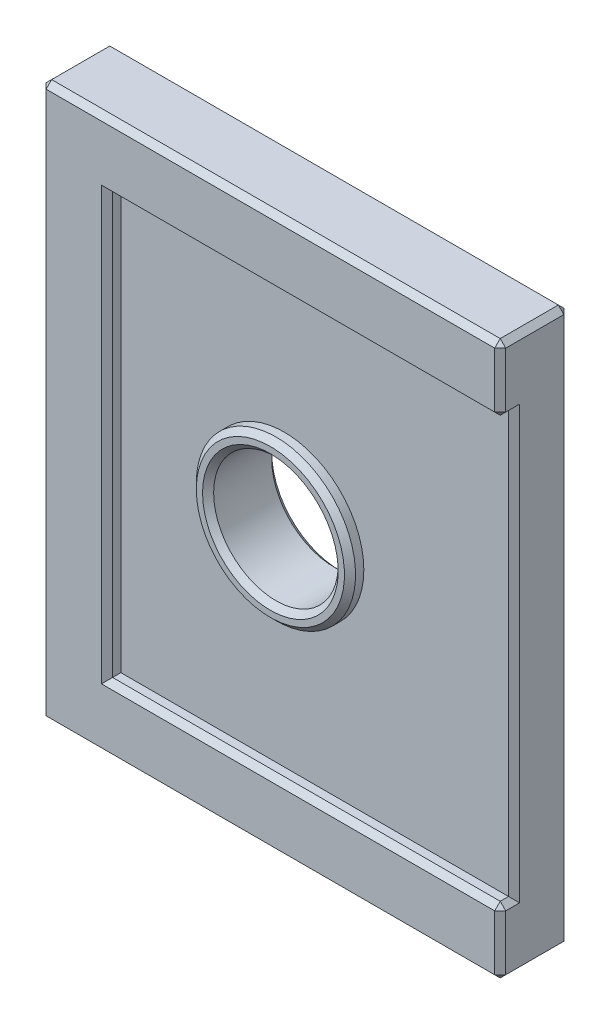
SolidWorks part; units mm, degrees
ref_plane "Front" through (0, 0, 0) normal (0, 0, 1) x (1, 0, 0)
ref_plane "Top" through (0, 0, 0) normal (0, 1, 0) x (1, 0, 0)
ref_plane "Right" through (0, 0, 0) normal (1, 0, 0) x (0, 0, -1)
sketch "Sketch1" plane through (0, 0, 0) normal (0, 0, 1) x (1, 0, 0)
  line L0 (10.1535, 7.5) -> (-5.8, 7.5) construction
  line L1 (-8.3, 10) -> (8.3, 10)
  line L2 (-8.3, 10) -> (-8.3, -10)
  line L3 (-8.3, -10) -> (8.3, -10)
  line L4 (8.3, 10) -> (8.3, -10)
  line L5 (-8.3, 10) -> (8.3, -10) construction
  line L6 (-8.3, -10) -> (8.3, 10) construction
  line L7 (-5.8, 7.5) -> (-5.8, -7.5) construction
  circle A2 centre (0, 0) radius 2.875
  circle A3 centre (0, 0) radius 2.875 construction
  point P0 (0, 0)
  dimension "D1" = 2.5
  dimension "D2" = 2.5
  dimension "D3" = 0.2
extrude "Boss-Extrude1" add sketch "Sketch1" against normal blind 2
sketch "Sketch2" plane through (0, 0, 0) normal (0, 0, 1) x (1, 0, 0)
  line L0 (8.3, 10) -> (-8.3, 10)
  line L1 (-8.3, 10) -> (-8.3, -10)
  line L2 (-8.3, -10) -> (8.3, -10)
extrude "Extrude-Thin1" add sketch "Sketch2" along normal blind 0.5 thin thin type one direction reverse wall 2.4
sketch "Sketch3" plane through (0, 0, 0) normal (0, 0, 1) x (1, 0, 0)
  circle A0 centre (0, 0) radius 2.875 construction
  circle A1 centre (0, 0) radius 2.875
extrude "Boss-Extrude2" add sketch "Sketch3" along normal up to surface (0.5 mm away) up to face at (0.6, 0, 0.5)
sketch "Sketch4" plane through (0, 0, -2) normal (0, 0, -1) x (-1, 0, 0)
  point P0 (0, 0)
hole_wizard "M4 Clearance Hole1" positions "Sketch4" profile "Sketch5" hole size "M4" standard "ANSI Metric" end condition through all
sketch "Sketch5" plane through (0, 0, -2) normal (1, 0, 0) x (0, 1, 0)
  line L0 (0, 0) -> (0, 2.5)
  line L1 (0, 2.5) -> (2.25, 2.5)
  line L2 (2.25, 2.5) -> (2.25, 0)
  line L5 (2.25, 0) -> (0, 0)
  line L11 (0, -6.35) -> (0, 107.95) construction
  dimension "Thru Hole Dia." = 4.5
  dimension "Thru Hole Depth" = 2.5
chamfer "Deburs" distance 0.2 angle 45 22 edges at (-2.875, 0, 0.5) (-2.25, 0, 0.5) (-8.3, 10, -0.75) (-8.3, -10, -0.75) (8.3, 7.6, 0.25) (8.3, 10, -0.75) (8.3, 0, 0) (8.3, -7.6, 0.25) (-8.3, 0, 0.5) (0, 10, 0.5) (8.3, 8.8, 0.5) (1.2, 7.6, 0.5) (-5.9, 0, 0.5) (1.2, -7.6, 0.5) (8.3, -8.8, 0.5) (0, -10, 0.5) (8.3, -10, -0.75) (0, 10, -2) (-8.3, 0, -2) (0, -10, -2) (8.3, 0, -2) (-2.25, 0, -2)
